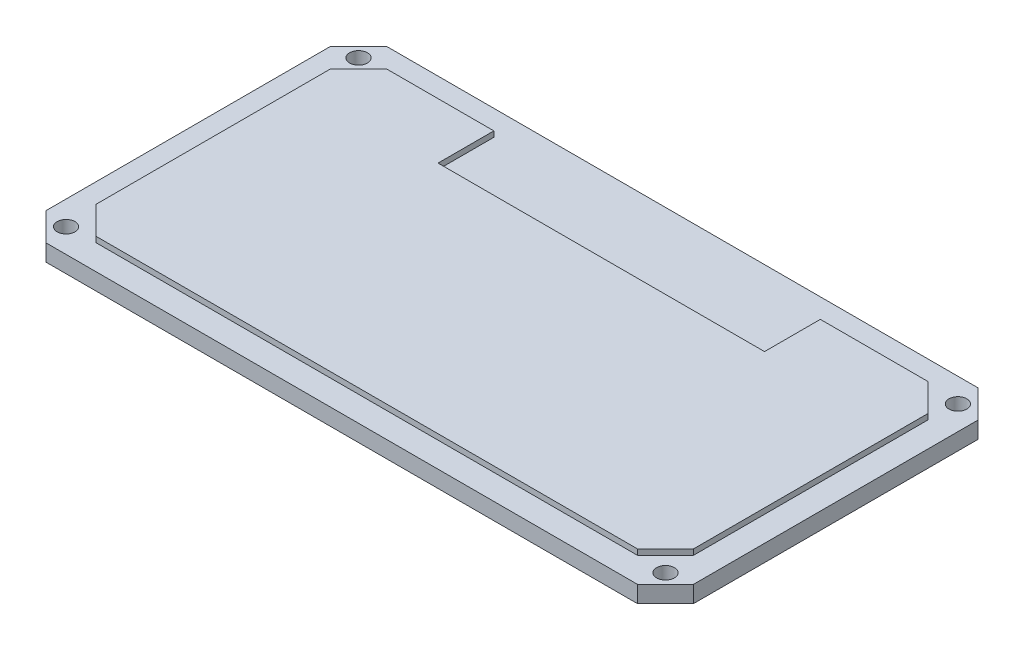
SolidWorks part; units mm, degrees
ref_plane "Front Plane" through (0, 0, 0) normal (0, 0, 1) x (1, 0, 0)
ref_plane "Top Plane" through (0, 0, 0) normal (0, 1, 0) x (1, 0, 0)
ref_plane "Right Plane" through (0, 0, 0) normal (1, 0, 0) x (0, 0, -1)
sketch "Sketch1" plane through (0, 0, 0) normal (0, 1, 0) x (1, 0, 0)
  line L1 (-58, 30.5) -> (58, 30.5)
  line L2 (-58, 30.5) -> (-58, -30.5)
  line L3 (-58, -30.5) -> (58, -30.5)
  line L4 (58, 30.5) -> (58, -30.5)
  line L5 (-58, 30.5) -> (58, -30.5) construction
  line L6 (-58, -30.5) -> (58, 30.5) construction
  point P0 (0, 0)
  dimension "D1" = 116
  dimension "D2" = 61
extrude "Boss-Extrude1" add sketch "Sketch1" along normal blind 3
chamfer "Chamfer1" distance 5 angle 45 4 edges at (-58, 1.5, -30.5) (58, 1.5, -30.5) (58, 1.5, 30.5) (-58, 1.5, 30.5)
sketch "Sketch2" plane through (0, 3, 0) normal (0, 1, 0) x (1, 0, 0)
  line L0 (53, 30.5) -> (-53, 30.5) construction
  line L1 (-58, 25.5) -> (-58, -25.5) construction
  line L2 (58, -25.5) -> (58, 25.5) construction
  line L3 (-53, -30.5) -> (53, -30.5) construction
  circle A0 centre (-53.7, 26.2) radius 1.6
  circle A1 centre (53.7, 26.2) radius 1.6
  circle A2 centre (53.7, -26.2) radius 1.6
  circle A3 centre (-53.7, -26.2) radius 1.6
  dimension "D1" = 3.2
  dimension "D2" = 4.3
  dimension "D3" = 4.3
  dimension "D4" = 3.2
  dimension "D5" = 4.3
  dimension "D6" = 4.3
  dimension "D7" = 3.2
  dimension "D8" = 4.3
  dimension "D9" = 4.3
  dimension "D10" = 3.2
  dimension "D11" = 4.3
  dimension "D12" = 4.3
extrude "Cut-Extrude1" cut sketch "Sketch2" against normal blind 10
sketch "Sketch3" plane through (0, 3, 0) normal (0, 1, 0) x (1, 0, 0)
  line L0 (53, 30.5) -> (-53, 30.5) construction
  line L1 (-53.5, 26) -> (53.5, 26)
  line L2 (-53.5, 26) -> (-53.5, -26)
  line L3 (-53.5, -26) -> (53.5, -26)
  line L4 (53.5, 26) -> (53.5, -26)
  line L5 (-53.5, 26) -> (53.5, -26) construction
  line L6 (-53.5, -26) -> (53.5, 26) construction
  line L7 (58, -25.5) -> (58, 25.5) construction
  point P0 (0, 0)
  dimension "D1" = 4.5
  dimension "D2" = 4.5
extrude "Boss-Extrude2" add sketch "Sketch3" along normal blind 1
chamfer "Chamfer2" distance 5 angle 45 4 edges at (53.5, 3.5, 26) (53.5, 3.5, -26) (-53.5, 3.5, 26) (-53.5, 3.5, -26)
sketch "Sketch4" plane through (0, 4, 0) normal (0, 1, 0) x (1, 0, 0)
  line L0 (48.5, 26) -> (-48.5, 26) construction
  line L1 (29.25, 26) -> (-29.25, 26)
  line L2 (29.25, 26) -> (29.25, 16)
  line L3 (29.25, 16) -> (-29.25, 16)
  line L4 (-29.25, 26) -> (-29.25, 16)
  line L5 (58, -25.5) -> (58, 25.5) construction
  dimension "D1" = 10
  dimension "D2" = 58.5
  dimension "D3" = 28.75
extrude "Cut-Extrude2" cut sketch "Sketch4" against normal blind 1
